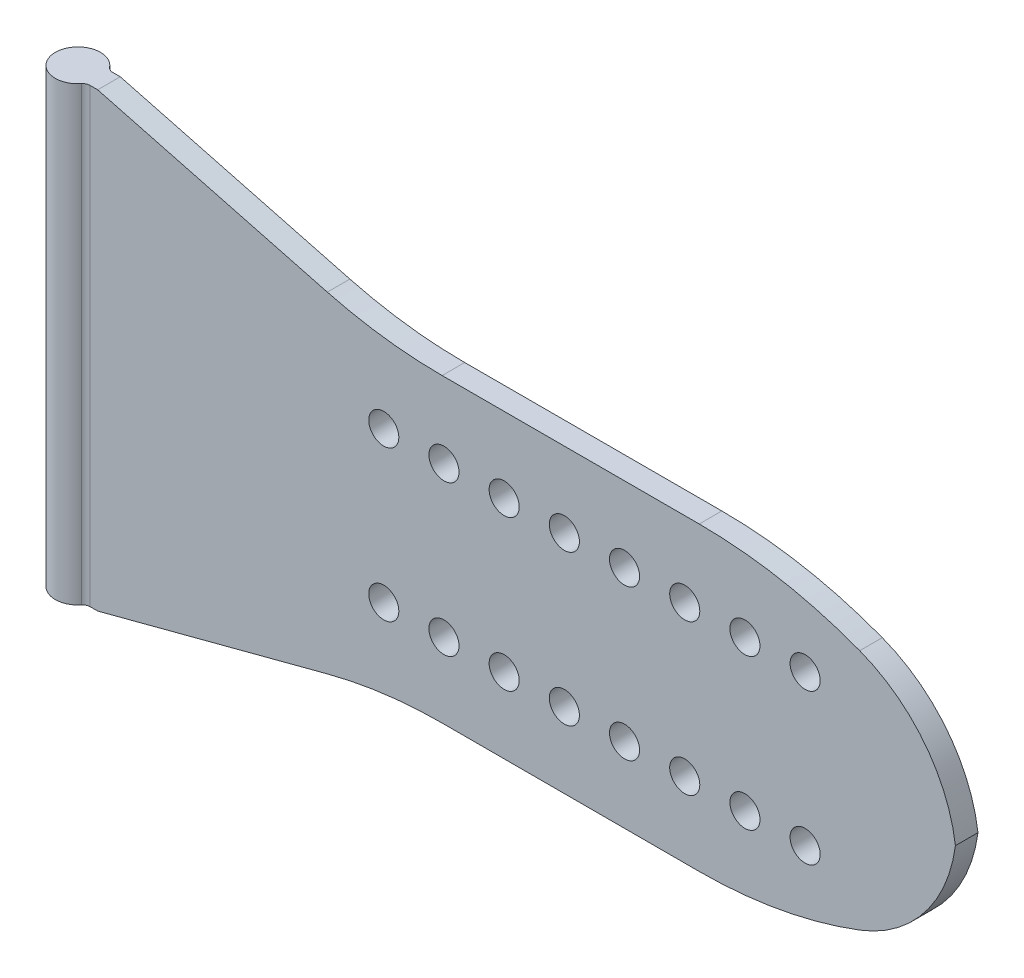
SolidWorks part; units mm, degrees
material "Silicon Rubber"
ref_plane "Front Plane" through (0, 0, 0) normal (0, 0, 1) x (1, 0, 0)
ref_plane "Top Plane" through (0, 0, 0) normal (0, 1, 0) x (1, 0, 0)
ref_plane "Right Plane" through (0, 0, 0) normal (1, 0, 0) x (0, 0, -1)
sketch "Sketch1" plane through (0, 0, 0) normal (0, 1, 0) x (1, 0, 0)
  line L0 (0, 0) -> (1.5612, 0) construction
  line L1 (1.5612, 1.25) -> (1.5612, -1.25) construction
  line L2 (1.5612, 0.75) -> (1.5612, -0.75) construction
  line L3 (1.5612, 0.75) -> (59.1512, 0.75)
  line L4 (59.1512, 0.75) -> (59.1512, -0.75)
  line L5 (59.1512, -0.75) -> (1.5612, -0.75)
  circle A0 centre (0, 0) radius 1.5 construction
  arc A1 (1.5612, 0.75) -> (1.1709, 0.9375) centre (1.5612, 1.25) cw
  arc A2 (1.5612, -0.75) -> (1.1709, -0.9375) centre (1.5612, -1.25) ccw
  arc A3 (1.1709, 0.9375) -> (1.1709, -0.9375) centre (0, 0) ccw
  point P7 (1.5612, 0)
  point P10 (1.5612, 0)
  dimension "D1" = 3
  dimension "D2" = 1.5
  dimension "D3" = 2.5
  dimension "D4" = 57.59
extrude "Boss-Extrude1" add sketch "Sketch1" along normal blind 15 and the other way blind 15
sketch "Sketch2" plane through (0, 0, 0.75) normal (0, 0, 1) x (1, 0, 0)
  line L0 (59.1512, -5) -> (59.1512, 5) construction
  line L1 (59.1512, -15) -> (59.1512, 15) construction
  line L2 (59.1512, 0) -> (49.0772, 0) construction
  line L3 (49.0772, 10) -> (49.0772, -10) construction
  line L4 (49.0772, 0) -> (2.0652, 0) construction
  line L5 (2.0652, -15) -> (2.0652, 15) construction
  line L6 (1.5612, 15) -> (59.1512, 15) construction
  line L7 (21.0772, 15) -> (21.0772, -15) construction
  line L8 (1.5612, -15) -> (59.1512, -15) construction
  line L9 (59.1512, 5) -> (2.0652, 5) construction
  line L10 (59.1512, -5) -> (2.0652, -5) construction
  line L11 (49.0772, 10) -> (21.0772, 10)
  line L12 (21.0772, 10) -> (2.0652, 15)
  line L13 (2.0652, 15) -> (59.1512, 15)
  line L14 (59.1512, 15) -> (59.1512, 5)
  line L15 (59.1512, 5) -> (49.0772, 10)
  line L16 (49.0772, -10) -> (21.0772, -10)
  line L17 (21.0772, -10) -> (2.0652, -15)
  line L18 (2.0652, -15) -> (59.1512, -15)
  line L19 (59.1512, -15) -> (59.1512, -5)
  line L20 (59.1512, -5) -> (49.0772, -10)
  circle A0 centre (49.0772, 5) radius 1
  circle A1 centre (45.0772, 5) radius 1
  circle A2 centre (41.0772, 5) radius 1
  circle A3 centre (37.0772, 5) radius 1
  circle A4 centre (33.0772, 5) radius 1
  circle A5 centre (29.0772, 5) radius 1
  circle A6 centre (25.0772, 5) radius 1
  circle A7 centre (21.0772, 5) radius 1
  circle A8 centre (45.0772, -5) radius 1
  circle A9 centre (41.0772, -5) radius 1
  circle A10 centre (37.0772, -5) radius 1
  circle A11 centre (33.0772, -5) radius 1
  circle A12 centre (29.0772, -5) radius 1
  circle A13 centre (25.0772, -5) radius 1
  circle A14 centre (21.0772, -5) radius 1
  circle A15 centre (49.0772, -5) radius 1
  point P5 (59.1512, 0)
  point P14 (2.0652, 0)
  point P17 (49.0772, 0)
  point P22 (21.0772, 0)
  dimension "D5" = 2
  dimension "D1" = 10
  dimension "10.074mm" = 10.074
  dimension "D2" = 20
  dimension "D3" = 47.012
  dimension "D4" = 28
  dimension "D6" = 8
  dimension "D7" = 2
extrude "Cut-Extrude1" cut sketch "Sketch2" against normal through all
fillet "Fillet1" radius 30 4 edges at (21.0772, -10, 0) (49.0772, -10, 0) (49.0772, 10, 0) (21.0772, 10, 0)
fillet "Fillet2" radius 10 2 edges at (59.1512, -5, 0) (59.1512, 5, 0)
